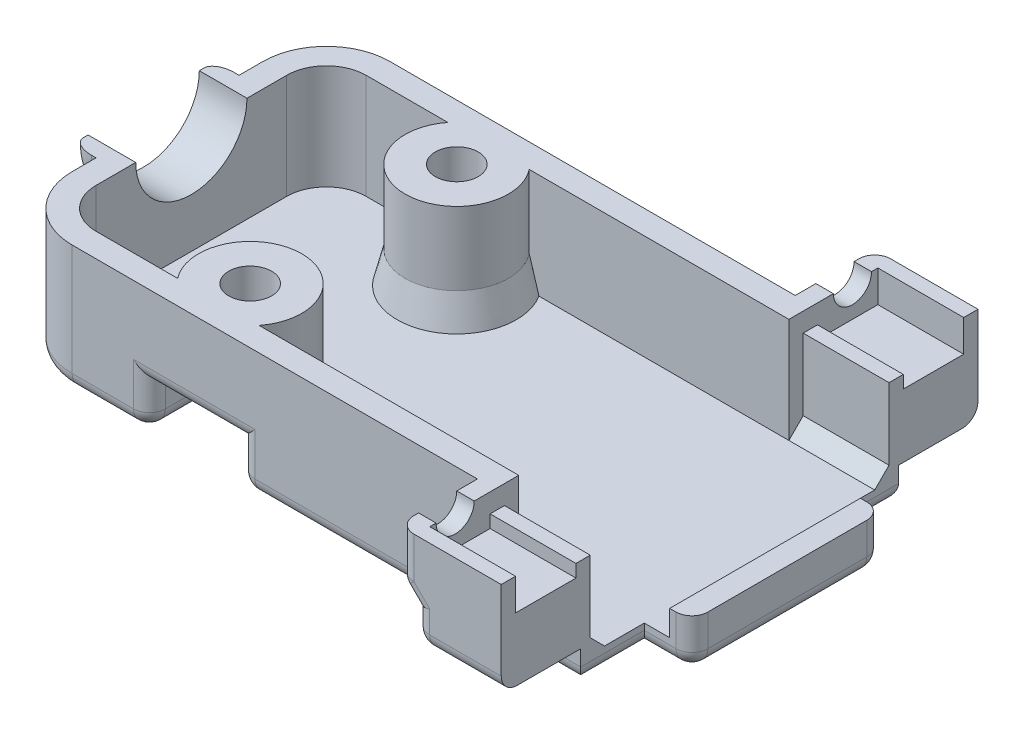
SolidWorks part; units mm, degrees
note: The reader was unsure of these and kept them because the rebuilt part matched: shared geometry of "Sketch9<4>".
ref_plane "Front Plane" through (0, 0, 0) normal (0, 0, 1) x (1, 0, 0)
ref_plane "Top Plane" through (0, 0, 0) normal (0, 1, 0) x (1, 0, 0)
ref_plane "Right Plane" through (0, 0, 0) normal (1, 0, 0) x (0, 0, -1)
sketch "Sketch1" plane through (0, 0, 0) normal (0, 1, 0) x (1, 0, 0)
  line L0 (16.5, 10) -> (16.5, 6)
  line L1 (19.5, -10) -> (-15.5, -10)
  line L2 (19.5, -10) -> (19.5, 10)
  line L3 (19.5, 10) -> (-15.5, 10)
  line L4 (-19.5, -6) -> (-19.5, 6)
  line L5 (19.5, -10) -> (-19.5, 10) construction
  line L6 (19.5, 10) -> (-19.5, -10) construction
  line L7 (16.5, 6) -> (19.5, 6)
  line L8 (19.5, -6) -> (16.5, -6)
  line L9 (16.5, -6) -> (16.5, -10)
  line L10 (0, 0) -> (11.9213, 0) construction
  arc A0 (-15.5, -10) -> (-19.5, -6) centre (-15.5, -6) cw
  arc A1 (-15.5, 10) -> (-19.5, 6) centre (-15.5, 6) ccw
  point P0 (0, 0)
  dimension "D5" = 4
  dimension "D1" = 39
  dimension "D2" = 20
  dimension "D3" = 12
  dimension "D4" = 3
extrude "Base" add sketch "Sketch1" along normal blind 8 contours L9 L8 L2 L7 L0 L3 L4 L1
sketch "Sketch4" plane through (0, 0, 0) normal (0, -1, 0) x (1, 0, 0)
  line L0 (-19.5, 6) -> (-19.5, -6) construction
  line L1 (1.5, 6) -> (7.5, 6)
  line L2 (0.5, 5) -> (0.5, -5)
  line L3 (1.5, -6) -> (7.5, -6)
  line L4 (8.5, 5) -> (8.5, -5)
  line L5 (0.5, 6) -> (8.5, -6) construction
  line L6 (0.5, -6) -> (8.5, 6) construction
  arc A0 (0.5, -5) -> (1.5, -6) centre (1.5, -5) ccw
  arc A1 (7.5, -6) -> (8.5, -5) centre (7.5, -5) ccw
  arc A2 (7.5, 6) -> (8.5, 5) centre (7.5, 5) cw
  arc A3 (1.5, 6) -> (0.5, 5) centre (1.5, 5) ccw
  point P0 (4.5, 0)
  dimension "D4" = 1
  dimension "D1" = 12
  dimension "D2" = 8
  dimension "D3" = 20
extrude "LogoPlace" cut sketch "Sketch4" against normal blind 0.5
sketch "Sketch5" plane through (0, 0, 0) normal (0, 0, 1) x (1, 0, 0)
  line L0 (16.5, 8.5064) -> (16.5, 1.4)
  line L1 (16.5, 8) -> (16.5, 0) construction
  line L2 (16.5, 1.4) -> (18.1, 1.4)
  line L3 (18.1, 1.4) -> (18.1, 3)
  line L4 (18.1, 3) -> (19.8906, 3)
  line L5 (19.8906, 3) -> (19.8906, 8.5064)
  line L6 (19.8906, 8.5064) -> (16.5, 8.5064)
  line L7 (19.5, 8) -> (19.5, 0) construction
  line L8 (19.5, 0) -> (16.5, 0) construction
  dimension "D1" = 1.4
  dimension "D2" = 1.4
  dimension "D3" = 3
extrude "ConnectorPlace" cut sketch "Sketch5" against normal mid plane 25
sketch "Sketch2" plane through (0, 0, 10) normal (0, 0, 1) x (1, 0, 0)
  line L0 (16.5, 8) -> (16.5, 2)
  line L1 (16.5, 1.4) -> (16.5, 0) construction
  line L2 (16.5, 2) -> (11, 2)
  line L3 (11, 2) -> (11, 4)
  line L4 (11, 4) -> (10, 5)
  line L5 (10, 5) -> (10, 8)
  line L6 (16.5, 8) -> (-15.5, 8) construction
  line L7 (10, 8) -> (16.5, 8)
  dimension "D1" = 6
  dimension "D2" = 5.5
  dimension "D3" = 6.5
  dimension "D4" = 3
  dimension "D5" = 2
extrude "Boss-Extrude2" add sketch "Sketch2" along normal blind 5
sketch "Sketch6" plane through (0, 8, 0) normal (0, 1, 0) x (1, 0, 0)
  line L4 (11.5, -8.5) -> (16.5, -8.5)
  line L13 (16.5, 10) -> (16.5, -15) construction
  line L22 (16.5, 8.5) -> (16.5, -8.5)
  line L29 (11.5, -8.5) -> (-15.5, -8.5)
  line L30 (-18, -6) -> (-18, 6)
  line L32 (-15.5, 8.5) -> (16.5, 8.5)
  line L36 (11.5, -8.5) -> (16.5, -8.5)
  line L37 (0, 0) -> (-6.671, 0) construction
  line L38 (-19.5, -6) -> (-19.5, 6) construction
  arc A11 (-10.3617, 8.5) -> (-5.2383, 8.5) centre (-7.8, 6.5) ccw
  arc A12 (-5.2383, -8.5) -> (-10.3617, -8.5) centre (-7.8, -6.5) ccw
  arc A15 (-18, -6) -> (-15.5, -8.5) centre (-15.5, -6) ccw
  arc A16 (-15.5, 8.5) -> (-18, 6) centre (-15.5, 6) ccw
  dimension "D4" = 6.5
  dimension "D5" = 13
  dimension "D6" = 11.7
  dimension "D1" = 1.5
extrude "Cut-Extrude4" cut sketch "Sketch6" against normal up to surface (6.6 mm away)
chamfer "Chamfer1" distance 0.5 angle 76 2 edges at (-7.8, 1.4, 3.25) (-7.8, 1.4, -3.25)
sketch "Sketch3" plane through (0, 0, 0) normal (0, -1, 0) x (1, 0, 0)
  line L0 (-10.6388, 10) -> (-4.9888, 10)
  line L1 (16.5, 10) -> (-15.5, 10) construction
  line L2 (-4.9888, 10) -> (-4.9888, 4.9)
  line L3 (-4.9888, 4.9) -> (-7.8138, 3.269)
  line L4 (-7.8138, 3.269) -> (-10.6388, 4.9)
  line L5 (-10.6388, 4.9) -> (-10.6388, 10)
  line L6 (0, 0) -> (-6.5861, 0) construction
  line L8 (-7.8138, 10) -> (-7.8138, 3.269) construction
  dimension "D1" = 5.65
  dimension "D2" = 60
  dimension "D3" = 5.1
extrude "NutHolder" cut sketch "Sketch3" against normal blind 2.7
sketch "Sketch7" plane through (16.5, 0, 0) normal (1, 0, 0) x (0, 0, -1)
  line L13 (0, 0) -> (0, 3) construction
  line L14 (6, 3) -> (-6, 3) construction
  line L15 (-14.1, 8.5556) -> (-14.1, 8)
  line L16 (-8.5, 8.5556) -> (-14.1, 8.5556)
  line L17 (-8.5, 1.4) -> (-8.5, 8.5556)
  line L18 (-9.4, 2.3) -> (-8.5, 1.4)
  line L19 (-9.4, 6.8) -> (-9.4, 2.3)
  line L20 (-10.3, 6.8) -> (-9.4, 6.8)
  line L21 (-10.3, 6) -> (-10.3, 6.8)
  line L22 (-14.1, 6) -> (-10.3, 6)
  line L23 (-14.1, 8) -> (-14.1, 6)
extrude "Cut-Extrude5" cut sketch "Sketch7" against normal blind 5.4
sketch "Sketch8" plane through (10, 0, 0) normal (-1, 0, 0) x (0, 0, 1)
  line L1 (15, 8) -> (10, 8) construction
  circle A0 centre (12.5, 8) radius 1.2
  dimension "D1" = 2.4
extrude "ForScrew" cut sketch "Sketch8" against normal blind 5.4
sketch "Sketch9" plane through (-19.5, 0, 0) normal (-1, 0, 0) x (0, 0, 1)
  line L0 (6, 8) -> (-6, 8) construction
  line L1 (-4.5, 8) -> (-3.5, 8)
  line L2 (3.5, 8) -> (4.5, 8)
  line L3 (-3.5, 8) -> (3.5, 8)
  arc A0 (-4.5, 8) -> (4.5, 8) centre (0, 8) ccw
  arc A1 (-3.5, 8) -> (3.5, 8) centre (0, 8) ccw
  line M3 (6, 8) -> (-6, 8)
  dimension "D1" = 9
  dimension "D2" = 7
extrude "CableHole" cut sketch "Sketch9" against normal blind 5.4 contours A1 M3
extrude "Boss-Extrude3" add sketch "Sketch9<4>" along normal blind 1.5 contours A1 A0 M3
sketch "Sketch9<4>" plane through (-19.5, 0, 0) normal (-1, 0, 0) x (0, 0, 1) same geometry as "Sketch9"
mirror "Mirror1" about plane through (0, 0, 0) normal (0, 0, 1) of "ForScrew", "Cut-Extrude5", "Boss-Extrude2", "NutHolder"
fillet "CableFillet" radius 1.2 1 edges at (-21, 3.5, 0)
sketch "Sketch10" plane through (0, 8, 0) normal (0, 1, 0) x (1, 0, 0)
  circle A0 centre (-7.8, 6.5) radius 1.35
  circle A1 centre (-7.8, -6.5) radius 1.35
  dimension "D1" = 2.7
extrude "MountHoles" cut sketch "Sketch10" against normal blind 11.7
fillet "FilletAll" radius 1 39 edges at (19.5, 1.5, 6) (19.5, 1.5, -6) (-10.6388, 1.35, 10) (-7.8138, 2.7, 10) (-4.9888, 1.35, 10) (-13.0694, 0, -10) (-18.3284, 0, -8.8284) (-18.3284, 0, 8.8284) (-13.0694, 0, 10) (-10.6388, 0, 7.45) (-9.2263, 0, 4.0845) (-6.4013, 0, 4.0845) (-4.9888, 0, 7.45) (5.7556, 0, 10) (16.5, 0, -8) (18, 0, 6) (19.5, 0, 0) (18, 0, -6) (5.7556, 0, -10) (-19.5, 0, 0) (11, 3, 15) (10.5, 4.5, 15) (10, 6.5, 15) (10, 5, 12.5) (11, 2, 12.5) (13.75, 2, 15) (-4.9888, 1.35, -10) (-10.6388, 1.35, -10) (-7.8138, 2.7, -10) (-4.9888, 0, -7.45) (-6.4013, 0, -4.0845) (-9.2263, 0, -4.0845) (-10.6388, 0, -7.45) (10, 6.5, -15) (10.5, 4.5, -15) (11, 3, -15) (13.75, 2, -15) (10, 5, -12.5) (11, 2, -12.5)
